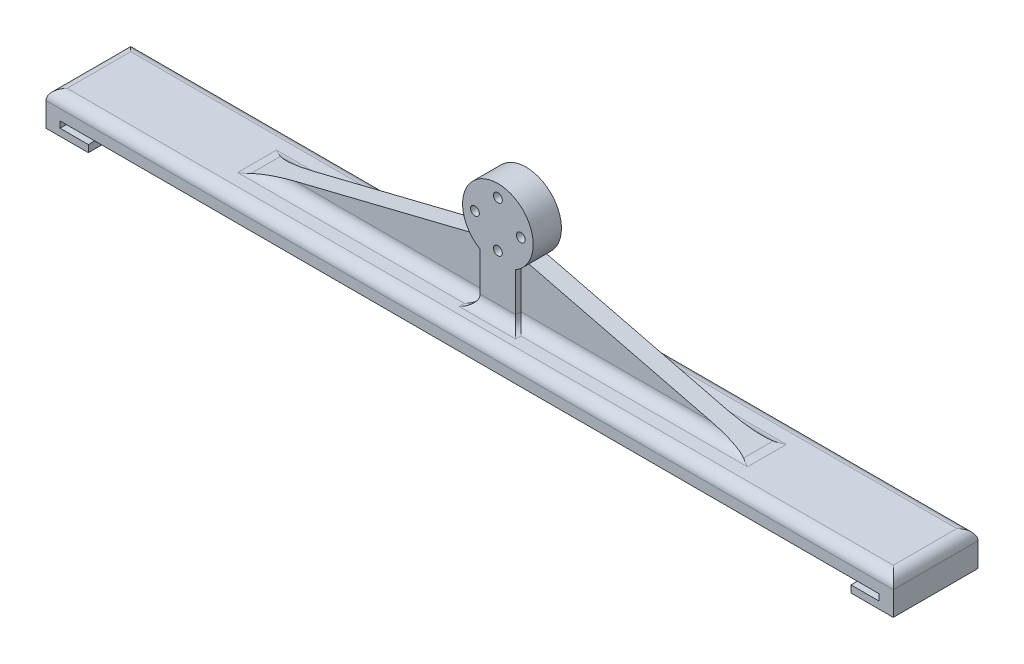
SolidWorks part; units mm, degrees
ref_plane "Front Plane" through (0, 0, 0) normal (0, 0, 1) x (1, 0, 0)
ref_plane "Top Plane" through (0, 0, 0) normal (0, 1, 0) x (1, 0, 0)
ref_plane "Right Plane" through (0, 0, 0) normal (1, 0, 0) x (0, 0, -1)
sketch "Sketch1" plane through (0, 0, 0) normal (0, 0, 1) x (1, 0, 0)
  circle A0 centre (0, 0) radius 10
  dimension "D1" = 20
extrude "Boss-Extrude1" add sketch "Sketch1" along normal blind 8
sketch "Sketch2" plane through (0, 0, 8) normal (0, 0, 1) x (1, 0, 0)
  circle A0 centre (0, 0) radius 6.5 construction
  circle A1 centre (0, 6.5) radius 1.25
  circle A2 centre (6.5, 0) radius 1.25
  circle A3 centre (0, -6.5) radius 1.25
  circle A4 centre (-6.5, 0) radius 1.25
  point P14 (0, 0)
  dimension "D1" = 13
  dimension "D2" = 2.5
  dimension "D3" = 4
extrude "Cut-Extrude1" cut sketch "Sketch2" against normal through all
sketch "Sketch3" plane through (0, 0, 0) normal (0, 0, -1) x (-1, 0, 0)
  circle A0 centre (0, 0) radius 2.5
  dimension "D1" = 5
extrude "Cut-Extrude2" cut sketch "Sketch3" against normal blind 2
ref_plane "Plane1" through (0, 0, 4) normal (0, 0, 1) x (1, 0, 0)
sketch "草图2" plane through (0, 0, 4) normal (0, 0, 1) x (1, 0, 0)
  line L0 (-5, -8.6603) -> (-5, -26.6603)
  line L1 (-5, -26.6603) -> (5, -26.6603)
  line L2 (5, -26.6603) -> (5, -8.6603)
  line L3 (0, -26.6603) -> (0, -24.4303) construction
  circle A0 centre (0, 0) radius 10 construction
  arc A1 (-5, -8.6603) -> (5, -8.6603) centre (0, 0) ccw
  dimension "D1" = 18
  dimension "D2" = 10
extrude "凸台-拉伸1" add sketch "草图2" along normal blind 4 and the other way blind 4
sketch "草图3" plane through (0, -26.6603, 0) normal (0, -1, 0) x (1, 0, 0)
  line L0 (0, 8) -> (0, 0) construction
  line L1 (-5, 8) -> (5, 8) construction
  line L2 (-5, 0) -> (5, 0) construction
  line L4 (-116, 16) -> (116, 16)
  line L5 (-116, 16) -> (-116, -8)
  line L6 (-116, -8) -> (116, -8)
  line L7 (116, 16) -> (116, -8)
  line L8 (-116, 16) -> (116, -8) construction
  line L9 (-116, -8) -> (116, 16) construction
  line L11 (10, 8) -> (-10, 8) construction
  point P6 (0, 4)
  point P7 (0, 4)
  dimension "D1" = 116
  dimension "D2" = 8
extrude "凸台-拉伸2" add sketch "草图3" along normal blind 2
sketch "草图4" plane through (0, 0, 16) normal (0, 0, 1) x (1, 0, 0)
  line L0 (116, -26.6603) -> (120, -26.6603)
  line L1 (120, -26.6603) -> (120, -32.4603)
  line L2 (120, -32.4603) -> (108, -32.4603)
  line L3 (108, -32.4603) -> (108, -30.4603)
  line L4 (108, -30.4603) -> (116, -30.4603)
  line L5 (116, -30.4603) -> (116, -28.6603)
  line L6 (116, -28.6603) -> (-116, -28.6603) construction
  line L8 (116, -26.6603) -> (116, -28.6603)
  line L12 (116, -26.6603) -> (-116, -26.6603)
  line L13 (-116, -26.6603) -> (-116, -28.6603)
  line L14 (-116, -28.6603) -> (116, -28.6603)
  line L15 (116, -28.6603) -> (116, -26.6603)
  line L16 (116, -26.6603) -> (-116, -26.6603)
  line L17 (-116, -26.6603) -> (-116, -28.6603)
  line L18 (-116, -28.6603) -> (116, -28.6603)
  line M7 (116, -28.6603) -> (116, -26.6603)
  dimension "D1" = 1.8
  dimension "D2" = 2
  dimension "D3" = 4
  dimension "D4" = 8
  dimension "D5" = 0
ref_plane "基准面1" through (0, 0, 0) normal (-1, 0, 0) x (0, 0, 1)
extrude "凸台-拉伸3" add sketch "草图4" against normal up to surface (24 mm away) contours L5 L4 L3 L2 L1 L0 M7 region at (118, -26.7935, 16) up to face at (0, -27.6603, -8)
mirror "镜向1" about plane through (0, 0, 0) normal (-1, 0, 0) of "凸台-拉伸3"
sketch "草图5" plane through (0, -26.6603, 0) normal (0, 1, 0) x (1, 0, 0)
  line L4 (-120, -16) -> (120, -16)
  line L5 (120, -16) -> (120, 8)
  line L6 (120, 8) -> (-120, 8)
  line L7 (-120, 8) -> (-120, -16)
  line L8 (-120, -16) -> (120, -16)
  line L9 (120, -16) -> (120, 8)
  line L10 (120, 8) -> (-120, 8)
  line L11 (-120, 8) -> (-120, -16)
  line M5 (-120, -16) -> (120, -16)
  line M6 (120, -16) -> (120, 8)
  line M7 (120, 8) -> (-120, 8)
  line M8 (-120, 8) -> (-120, -16)
  line M9 (-5, 0) -> (5, 0)
  line M10 (5, 0) -> (5, -8)
  line M11 (5, -8) -> (-5, -8)
  line M12 (-5, -8) -> (-5, 0)
  dimension "D1" = 0
extrude "凸台-拉伸4" add sketch "草图5" along normal blind 4 contours M8 M5 M6 M7 M12 M9 M10 M11 | L8 L9 L10 L11 region at (-117.588, -26.6603, 4)
sketch "草图6" plane through (0, 0, 4) normal (0, 0, -1) x (-1, 0, 0)
  line L0 (6.3676, -6.6424) -> (70.9854, -22.6603)
  line L1 (-120, -22.6603) -> (120, -22.6603) construction
  point P5 (5, -8.6603)
  point P6 (6.3676, -6.6424)
rib "筋1" sketch "草图6" sketch "草图6" thickness 5 extrusion direction parallel to sketch draft on no parameters "D1"=5
mirror "镜向2" about plane through (0, 0, 0) normal (-1, 0, 0) of "筋1"
fillet "圆角1" radius 10 2 edges at (70.9854, -22.6603, 4) (-70.9854, -22.6603, 4)
fillet "圆角3" radius 3 14 edges at (5, -22.6603, 0.75) (0, -22.6603, 0) (-5, -22.6603, 0.75) (-38.6032, -22.6603, 1.5) (-38.6032, -22.6603, 6.5) (-5, -22.6603, 7.25) (0, -22.6603, 8) (5, -22.6603, 7.25) (38.6032, -22.6603, 6.5) (38.6032, -22.6603, 1.5) (0, -22.6603, -8) (120, -22.6603, 4) (0, -22.6603, 16) (-120, -22.6603, 4)
